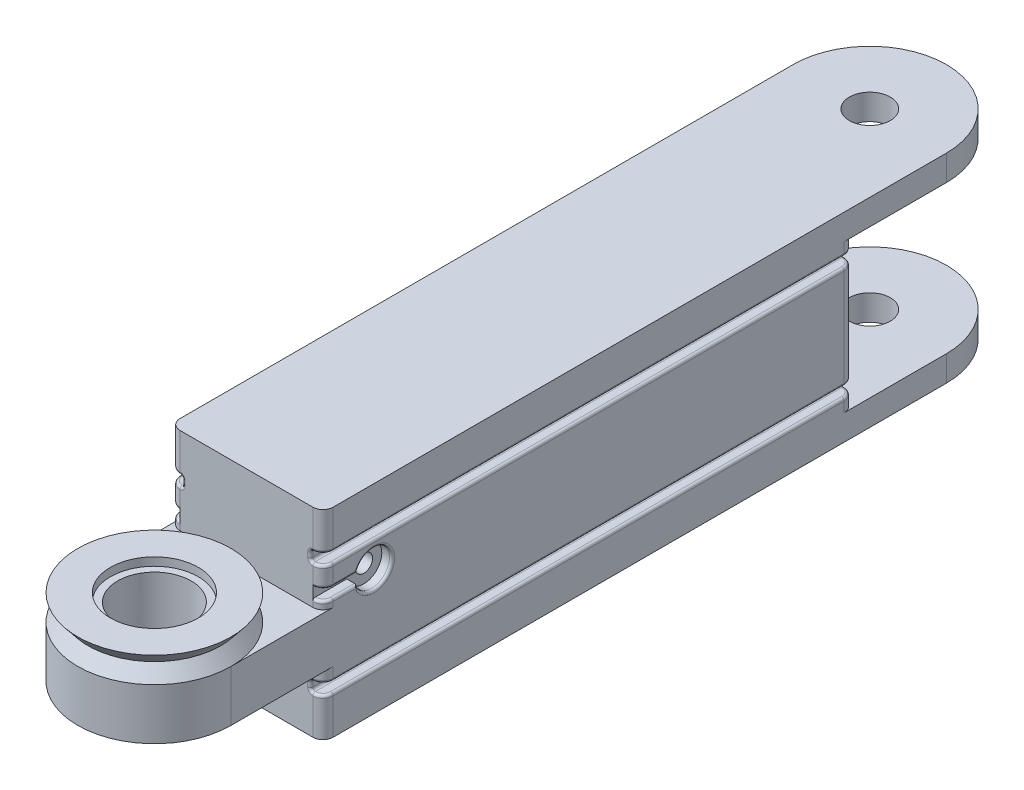
SolidWorks part; units mm, degrees
ref_plane "정면" through (0, 0, 0) normal (0, 0, 1) x (1, 0, 0)
ref_plane "윗면" through (0, 0, 0) normal (0, 1, 0) x (1, 0, 0)
ref_plane "우측면" through (0, 0, 0) normal (1, 0, 0) x (0, 0, -1)
sketch "스케치1" plane through (0, 0, 0) normal (0, 1, 0) x (1, 0, 0)
  line L0 (0, 0) -> (0, 70) construction
  line L1 (-7.5, 0) -> (-7.5, 70)
  line L2 (7.5, 0) -> (7.5, 70)
  arc A0 (-7.5, 0) -> (7.5, 0) centre (0, 0) ccw
  arc A1 (7.5, 70) -> (-7.5, 70) centre (0, 70) ccw
  point P3 (0, 35)
  dimension "D2" = 15
  dimension "D1" = 70
extrude "보스-돌출1" add sketch "스케치1" along normal blind 5
sketch "스케치2" plane through (0, 0, 0) normal (0, 0, 1) x (1, 0, 0)
  line L0 (0, 0) -> (0, 7.5) construction
  line L1 (0, -2.75) -> (0, 2.75) construction
  line L2 (0, 5) -> (0, 7.5)
  line L3 (7.5, 5) -> (-7.5, 5) construction
  line L4 (0, 7.5) -> (-7.5, 7.5)
  line L5 (-7.5, 7.5) -> (-6.5, 6.25)
  line L6 (-6.5, 6.25) -> (-7.5, 5)
  line L7 (-7.5, 5) -> (0, 5)
  line L8 (0, 5) -> (0.0142, 9.9699)
  point P16 (0, 6.25)
  dimension "D1" = 6.5
  dimension "D2" = 2.5
revolve "회전1" add sketch "스케치2" angle 360 about L0
sketch "스케치3" plane through (0, 5, 0) normal (0, 1, 0) x (1, 0, 0)
  line L0 (7.5, 70) -> (7.5, 9)
  line L2 (-7.5, 70) -> (-7.5, 9)
  line L4 (-7.5, 9) -> (7.5, 9)
  arc A0 (7.5, 70) -> (-7.5, 70) centre (0, 70) ccw
  arc A5 (7.5, 70) -> (-7.5, 70) centre (0, 70) ccw construction
  dimension "D1" = 9
extrude "보스-돌출3" add sketch "스케치3" along normal blind 8.5 and the other way offset from surface (11 mm away) 6 other way up to face at (0, 0, -35)
sketch "스케치4" plane through (0, 0, 0) normal (0, 1, 0) x (1, 0, 0)
  line L0 (-7.5, 70) -> (-7.5, 9) construction
  line L2 (7.5, 70) -> (7.5, 61)
  line L3 (7.5, 61) -> (-7.5, 61)
  line L4 (-7.5, 70) -> (-7.5, 61)
  arc A0 (7.5, 70) -> (-7.5, 70) centre (0, 70) ccw
  arc A1 (7.5, 70) -> (-7.5, 70) centre (0, 70) ccw construction
  dimension "D1" = 9
extrude "컷-돌출1" cut sketch "스케치4" along normal offset from surface 2.5 and the other way offset from surface (3.5 mm away) 2.5 up to face at (0, 13.5, -41.375) other way up to face at (0, -6, -41.375)
fillet "필렛1" radius 1 6 edges at (7.5, 3.75, -61) (-7.5, 3.75, -61) (7.5, -3, -9) (7.5, 9.25, -9) (-7.5, -3, -9) (-7.5, 9.25, -9)
sketch "스케치5" plane through (0, 0, -9) normal (0, 0, 1) x (1, 0, 0)
  line L0 (7.5, 13.5) -> (7.5, 5) construction
  line L1 (7.5, 6.75) -> (6.5, 6.75)
  line L2 (7.5, 6.75) -> (7.5, 5.75)
  line L3 (7.5, 5.75) -> (6.5, 5.75)
  line L4 (6.5, 6.75) -> (6.5, 5.75)
  line L5 (-7.5, 5) -> (-7.5, 13.5) construction
  line L6 (-7.5, 6.75) -> (-6.5, 6.75)
  line L7 (-7.5, 6.75) -> (-7.5, 5.75)
  line L8 (-7.5, 5.75) -> (-6.5, 5.75)
  line L9 (-6.5, 6.75) -> (-6.5, 5.75)
  line L10 (6.5, 6.25) -> (-6.5, 6.25) construction
  point P14 (-7.5, 6.25)
  point P15 (7.5, 6.25)
  dimension "D1" = 1
  dimension "D2" = 1
  dimension "D3" = 1
  dimension "D4" = 1
extrude "컷-돌출2" cut sketch "스케치5" against normal blind 5
sketch "스케치6" plane through (7.5, 0, 0) normal (1, 0, 0) x (0, 0, -1)
  line L0 (14, 6.75) -> (10, 6.75) construction
  line L1 (14, 5.75) -> (10, 5.75) construction
  line L2 (14, 6.75) -> (14, 5.75) construction
  circle A0 centre (14, 6.25) radius 0.5
extrude "컷-돌출3" cut sketch "스케치6" against normal up to surface (15 mm away) up to face at (-7.5, 4.0625, -30.5)
sketch "스케치7" plane through (7.5, 0, 0) normal (1, 0, 0) x (0, 0, -1)
  circle A0 centre (14, 6.25) radius 1.75
  dimension "D1" = 3.5
extrude "컷-돌출4" cut sketch "스케치7" against normal up to surface (1 mm away) up to face at (6.5, 6.25, -11.375)
sketch "스케치8" plane through (-7.5, 0, 0) normal (-1, 0, 0) x (0, 0, 1)
  circle A0 centre (-14, 6.25) radius 1.75
  dimension "D1" = 3.5
extrude "컷-돌출5" cut sketch "스케치8" against normal up to surface (1 mm away) up to face at (-6.5, 6.25, -11.375)
sketch "스케치9" plane through (0, 0, -9) normal (0, 0, 1) x (1, 0, 0)
  line L0 (-7.5, 6.75) -> (-7.5, 13.5) construction
  line L1 (-7.5, 9.75) -> (-6.25, 9.75)
  line L2 (-7.5, 9.75) -> (-7.5, 8.75)
  line L3 (-7.5, 8.75) -> (-6.25, 8.75)
  line L4 (-6.25, 9.75) -> (-6.25, 8.75)
  line L5 (7.5, 13.5) -> (7.5, 6.75) construction
  line L6 (7.5, 9.75) -> (6.25, 9.75)
  line L7 (7.5, 9.75) -> (7.5, 8.75)
  line L8 (7.5, 8.75) -> (6.25, 8.75)
  line L9 (6.25, 9.75) -> (6.25, 8.75)
  line L10 (7.5, 0) -> (7.5, -6) construction
  line L11 (7.5, -1.25) -> (6.25, -1.25)
  line L12 (7.5, -1.25) -> (7.5, -2.25)
  line L13 (7.5, -2.25) -> (6.25, -2.25)
  line L14 (6.25, -1.25) -> (6.25, -2.25)
  line L15 (-7.5, -6) -> (-7.5, 0) construction
  line L16 (-7.5, -1.25) -> (-6.25, -1.25)
  line L17 (-7.5, -1.25) -> (-7.5, -2.25)
  line L18 (-7.5, -2.25) -> (-6.25, -2.25)
  line L19 (-6.25, -1.25) -> (-6.25, -2.25)
  line L20 (-6.5, 5.75) -> (-7.5, 5.75) construction
  line L21 (8.25, 0) -> (-8.25, 0) construction
  dimension "D1" = 1.25
  dimension "D2" = 1
  dimension "D3" = 3
  dimension "D4" = 1.25
extrude "컷-돌출6" cut sketch "스케치9" against normal up to surface (52 mm away) up to face at (0, 3.75, -61)
fillet "필렛2" radius 0.25 50 edges at (7.2071, 9.75, -60.7071) (7.2071, 9.75, -9.2929) (7.2071, 8.75, -60.7071) (7.2071, 8.75, -9.2929) (7.2071, 6.75, -9.2929) (7.2071, 5.75, -9.2929) (7.2071, -1.25, -60.7071) (7.2071, -1.25, -9.2929) (7.2071, -2.25, -60.7071) (7.2071, -2.25, -9.2929) (-7.2071, 5.75, -9.2929) (-7.2071, 6.75, -9.2929) (-7.2071, 8.75, -60.7071) (-7.2071, 8.75, -9.2929) (-7.2071, 9.75, -60.7071) (-7.2071, 9.75, -9.2929) (-7.2071, -2.25, -60.7071) (-7.2071, -2.25, -9.2929) (-7.2071, -1.25, -60.7071) (-7.2071, -1.25, -9.2929) (7.5, 9.75, -35) (7.5, 8.75, -35) (7.5, 6.25, -15.75) (7.5, 6.75, -11.1615) (7.5, 5.75, -11.1615) (7.5, -1.25, -35) (7.5, -2.25, -35) (-7.5, 6.25, -15.75) (-7.5, 5.75, -11.1615) (-7.5, 6.75, -11.1615) (-7.5, 8.75, -35) (-7.5, 9.75, -35) (-7.5, -2.25, -35) (-7.5, -1.25, -35) (-6.25, 9.25, -61) (-6.25, 9.25, -9) (-6.25, -1.75, -61) (-6.25, -1.75, -9) (-6.25, 8.75, -35) (-6.25, -2.25, -35) (6.25, 9.25, -61) (6.25, 9.25, -9) (6.25, -1.75, -61) (6.25, -1.75, -9) (6.25, -1.25, -35) (6.25, 9.75, -35) (-6.25, 9.75, -35) (-6.25, -1.25, -35) (6.25, -2.25, -35) (6.25, 8.75, -35)
sketch "스케치10" plane through (0, 7.5, 0) normal (0, 1, 0) x (1, 0, 0)
  circle A0 centre (0, 0) radius 3.6
  dimension "D1" = 7.2
extrude "컷-돌출7" cut sketch "스케치10" against normal up to surface (7.5 mm away) up to face at (0, 0, -5.0143)
sketch "스케치11" plane through (0, -6, 0) normal (0, -1, 0) x (1, 0, 0)
  line L0 (0, -10.725) -> (0, 10.725) construction
  circle A0 centre (0, -70) radius 2
  arc A1 (-7.5, -70) -> (7.5, -70) centre (0, -70) ccw construction
  dimension "D1" = 4
extrude "컷-돌출8" cut sketch "스케치11" against normal up to surface (19.5 mm away) up to face at (0, 13.5, -30.8476)
sketch "스케치12" plane through (0, 0, 0) normal (0, -1, 0) x (1, 0, 0)
  circle A0 centre (0, 0) radius 4.3
  dimension "D1" = 8.6
extrude "컷-돌출9" cut sketch "스케치12" against normal blind 0.8
sketch "스케치13" plane through (0, 7.5, 0) normal (0, 1, 0) x (1, 0, 0)
  circle A0 centre (0, 0) radius 4.3
  dimension "D1" = 8.6
extrude "컷-돌출10" cut sketch "스케치13" against normal blind 0.8
sketch "스케치14" plane through (6.5, 0, 0) normal (1, 0, 0) x (0, 0, -1)
  circle A0 centre (14, 6.25) radius 0.85
  dimension "D1" = 1.7
extrude "컷-돌출11" cut sketch "스케치14" against normal up to surface (13 mm away) up to face at (-6.5, 6.25, -10.7449)
